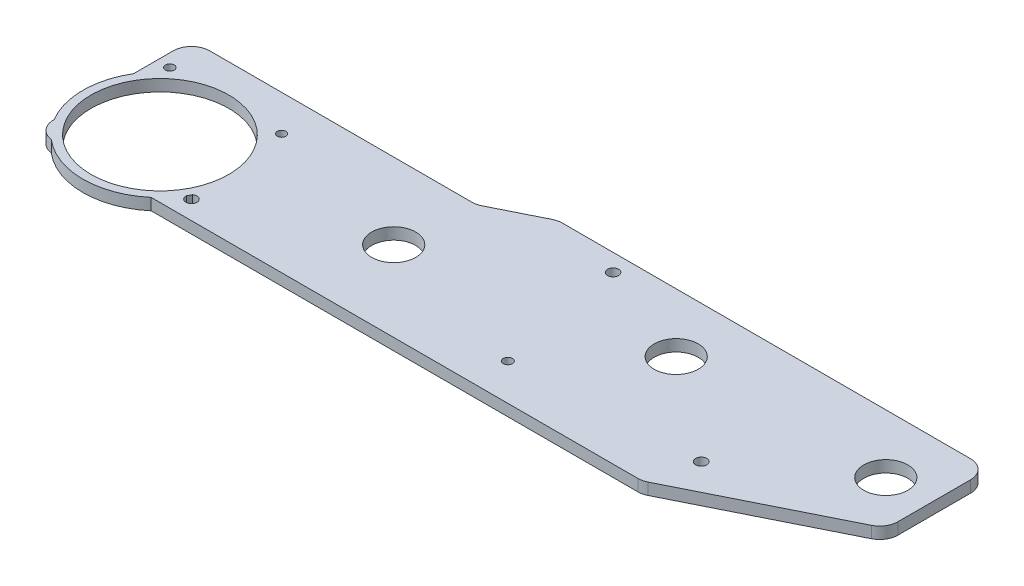
SolidWorks part; units mm, degrees
ref_plane "Front" through (0, 0, 0) normal (0, 0, 1) x (1, 0, 0)
ref_plane "Top" through (0, 0, 0) normal (0, 1, 0) x (1, 0, 0)
ref_plane "Right" through (0, 0, 0) normal (1, 0, 0) x (0, 0, -1)
sketch "Sketch1" plane through (0, 0, 0) normal (0, 1, 0) x (1, 0, 0)
  line L1 (0, 0) -> (210, 0)
  line L2 (0, 0) -> (0, -50)
  line L3 (0, -50) -> (210, -50)
  line L4 (210, 0) -> (210, -50)
  circle A7 centre (3.4895, -16.7877) radius 1.2117
  circle A8 centre (34.3726, -17.194) radius 1.1656
  circle A9 centre (37.5207, -44.9212) radius 1.5
  circle A10 centre (118.879, -40.0177) radius 1.25
  circle A11 centre (112.3021, -4.7393) radius 1.5
  circle A12 centre (168.9752, -37.4032) radius 1.5173
  dimension "D1" = 210
  dimension "D2" = 50
extrude "Boss-Extrude1" add sketch "Sketch1" along normal blind 3.175
sketch "Sketch2" plane through (0, 3.175, 0) normal (0, 1, 0) x (1, 0, 0)
  line L0 (210, 0) -> (0, 0) construction
  line L1 (0, 0) -> (0, -50) construction
  circle A0 centre (10, -26) radius 2
  circle A1 centre (10, -42) radius 2
  circle A2 centre (26, -26) radius 2
  circle A3 centre (26, -42) radius 2
  dimension "D1" = 16
  dimension "D2" = 16
  dimension "D3" = 16
  dimension "D4" = 26
  dimension "D5" = 10
  dimension "D6" = 10
  dimension "D7" = 26
  dimension "D8" = 16
extrude "Cut-Extrude1" cut sketch "Sketch2" against normal blind 10
sketch "Sketch3" plane through (0, 3.175, 0) normal (0, 1, 0) x (1, 0, 0)
  line L0 (210, 0) -> (0, 0) construction
  circle A0 centre (75.8499, -28.1) radius 6
  circle A1 centre (140.772, -16) radius 6
  circle A2 centre (18, -34) radius 0.587
  circle A3 centre (26, -26) radius 2 construction
  circle A4 centre (197.922, -16) radius 6
  dimension "D1" = 28.1
  dimension "D3" = 66.04
  dimension "D4" = 16
  dimension "D7" = 57.15
  dimension "D2" = 58.15
  dimension "D5" = 8
  dimension "D6" = 8
extrude "Cut-Extrude2" cut sketch "Sketch3" against normal blind 57.15
sketch "Sketch4" [suppressed] plane through (0, 3.175, 0) normal (0, 1, 0) x (1, 0, 0)
  line L0 (3.4895, -16.7877) -> (18, -34)
  line L1 (3.4895, -20.6627) -> (5.9498, -23.5811)
  line L2 (18, -34) -> (34.3726, -17.194)
  line L3 (34.3726, -17.194) -> (75.8499, -28.1)
  line L4 (75.8499, -28.1) -> (37.5207, -44.9212)
  line L5 (7.3432, -17.194) -> (9.8664, -20.303)
  circle A0 centre (18, -34) radius 15.9299
  circle A1 centre (3.4895, -16.7877) radius 3.8751
  circle A2 centre (34.3726, -17.194) radius 3.7227
  circle A3 centre (37.5207, -44.9212) radius 3.8676
  circle A4 centre (75.8499, -28.1) radius 12.797
  circle A5 centre (112.3021, -4.7393) radius 5.1588
  circle A6 centre (118.879, -40.0177) radius 4.9035
  circle A7 centre (140.772, -16) radius 12.6375
  circle A8 centre (168.9752, -37.4032) radius 4.2066
  circle A9 centre (197.922, -16) radius 12.8
sketch "Sketch5" [suppressed] plane through (0, 3.175, 0) normal (0, 1, 0) x (1, 0, 0)
  line L0 (210, 0) -> (0, 0) construction
  line L2 (-0.6266, -16.7877) -> (37.5207, -16.7877)
  line L3 (-0.6266, -16.7877) -> (-0.6266, -44.9212)
  line L4 (-0.6266, -44.9212) -> (37.5207, -44.9212)
  line L5 (37.5207, -16.7877) -> (37.5207, -44.9212)
  line L6 (75.8499, -15.182) -> (37.5207, -15.182)
  line L7 (75.8499, -15.182) -> (75.8499, -44.9212)
  line L8 (75.8499, -44.9212) -> (37.5207, -44.9212)
  line L9 (37.5207, -15.182) -> (37.5207, -44.9212)
  line L10 (112.3021, -4.7393) -> (75.8499, -4.7393)
  line L11 (112.3021, -4.7393) -> (112.3021, -44.9212)
  line L12 (112.3021, -44.9212) -> (75.8499, -44.9212)
  line L13 (75.8499, -4.7393) -> (75.8499, -44.9212)
  line L14 (112.3021, -4.7393) -> (102.3945, -4.7393)
  line L16 (112.3021, -4.7393) -> (112.3021, 0)
  line L17 (112.3021, 0) -> (102.3945, 0)
  line L18 (102.3945, -4.7393) -> (102.3945, 0)
  line L19 (210, -50) -> (210, 0) construction
  line L20 (112.3021, -4.7393) -> (123.1553, -4.7393)
  line L21 (112.3021, -4.7393) -> (112.3021, 0)
  line L22 (112.3021, 0) -> (123.1553, 0)
  line L23 (123.1553, -4.7393) -> (123.1553, 0)
  line L24 (112.3021, -4.7393) -> (140.772, -4.7393)
  line L25 (112.3021, -4.7393) -> (112.3021, -40.0177)
  line L26 (112.3021, -40.0177) -> (140.772, -40.0177)
  line L27 (140.772, -4.7393) -> (140.772, -40.0177)
  line L28 (140.772, -16) -> (168.9752, -16)
  line L29 (140.772, -16) -> (140.772, -40.0177)
  line L30 (140.772, -40.0177) -> (168.9752, -40.0177)
  line L31 (168.9752, -16) -> (168.9752, -40.0177)
  line L32 (168.9752, -4.7393) -> (210, -4.7393)
  line L33 (168.9752, -4.7393) -> (168.9752, -40.0177)
  line L34 (168.9752, -40.0177) -> (210, -40.0177)
  line L35 (210, -4.7393) -> (210, -40.0177)
  line L36 (0, -50) -> (210, -50) construction
  line L37 (160.7629, -40.0177) -> (177.2091, -40.0177)
  line L38 (160.7629, -40.0177) -> (160.7629, -44.9212)
  line L39 (160.7629, -44.9212) -> (177.2091, -44.9212)
  line L40 (177.2091, -40.0177) -> (177.2091, -44.9212)
  line L41 (112.3021, -40.0177) -> (126.3591, -40.0177)
  line L42 (112.3021, -40.0177) -> (112.3021, -47.7828)
  line L43 (112.3021, -47.7828) -> (126.3591, -47.7828)
  line L44 (126.3591, -40.0177) -> (126.3591, -47.7828)
  line L45 (30.5963, -44.9212) -> (44.6115, -44.9212)
  line L46 (30.5963, -44.9212) -> (30.5963, -50)
  line L47 (30.5963, -50) -> (44.6115, -50)
  line L48 (44.6115, -44.9212) -> (44.6115, -50)
  line L50 (-0.6266, -44.9212) -> (30.5963, -44.9212)
  line L51 (-0.6266, -44.9212) -> (-0.6266, -50)
  line L52 (-0.6266, -50) -> (30.5963, -50)
  line L53 (30.5963, -44.9212) -> (30.5963, -50)
  circle A0 centre (3.4895, -16.7877) radius 4.1161
  circle A1 centre (34.3726, -17.194) radius 3.8132
  circle A2 centre (75.8499, -28.1) radius 12.918
  circle A3 centre (112.3021, -4.7393) radius 5.2663
  circle A4 centre (140.772, -16) radius 13.0245
  circle A5 centre (197.922, -16) radius 12.3805
  circle A6 centre (168.9752, -37.4032) radius 4.7643
  circle A7 centre (118.879, -40.0177) radius 5.279
  circle A8 centre (37.5207, -44.9212) radius 4.2049
  line M12 (0, 0) -> (0, -50)
  line M13 (0, -50) -> (210, -50)
  line M14 (210, -50) -> (210, 0)
  line M15 (210, 0) -> (0, 0)
extrude "Cut-Extrude5" [suppressed] cut sketch "Sketch5" against normal blind 11.52 contours A5 L32 L23 L24 A4 L28 L33 M14 M15 | A1 L6 L13 L10 L18 A0 L2 M15 M12 | L8 L48 L34 L40 L39 L38 L30 L26 L44 L43 L42 L12 M13 M14
fillet "Fillet1" [suppressed] radius 5
sketch "Sketch10" plane through (0, 3.175, 0) normal (0, 1, 0) x (1, 0, 0)
  line L0 (210, -27.8594) -> (165.5029, -50)
  line L1 (210, -50) -> (210, 0) construction
  line L2 (0, -50) -> (210, -50) construction
  line L3 (165.5029, -50) -> (210, -50)
  line L4 (210, -50) -> (210, -27.8594)
  line L5 (92.5326, 0) -> (77.6548, -7.4028)
  line L6 (210, 0) -> (0, 0) construction
  line L7 (77.6548, -7.4028) -> (0, -7.4028)
  line L8 (0, 0) -> (0, -50) construction
  line L9 (0, -7.4028) -> (0, 0)
  line L10 (0, 0) -> (92.5326, 0)
extrude "Cut-Extrude7" cut sketch "Sketch10" against normal blind 10
fillet "Fillet3" radius 5 7 edges at (0, 1.5875, 50) (0, 1.5875, 7.4028) (77.6548, 1.5875, 7.4028) (92.5326, 1.5875, 0) (210, 1.5875, 0) (210, 1.5875, 27.8594) (165.5029, 1.5875, 50)
sketch "Sketch11" plane through (0, 3.175, 0) normal (0, 1, 0) x (1, 0, 0)
  circle A0 centre (18, -34) radius 21
  circle A1 centre (10, -26) radius 2
  circle A2 centre (10, -42) radius 2
  circle A3 centre (26, -26) radius 2
  circle A4 centre (26, -42) radius 2
extrude "Boss-Extrude4" add sketch "Sketch11" against normal blind 3.175
sketch "Sketch12" plane through (0, 3.175, 0) normal (0, 1, 0) x (1, 0, 0)
  circle A0 centre (18, -34) radius 18.78
extrude "Cut-Extrude8" cut sketch "Sketch12" against normal blind 10
